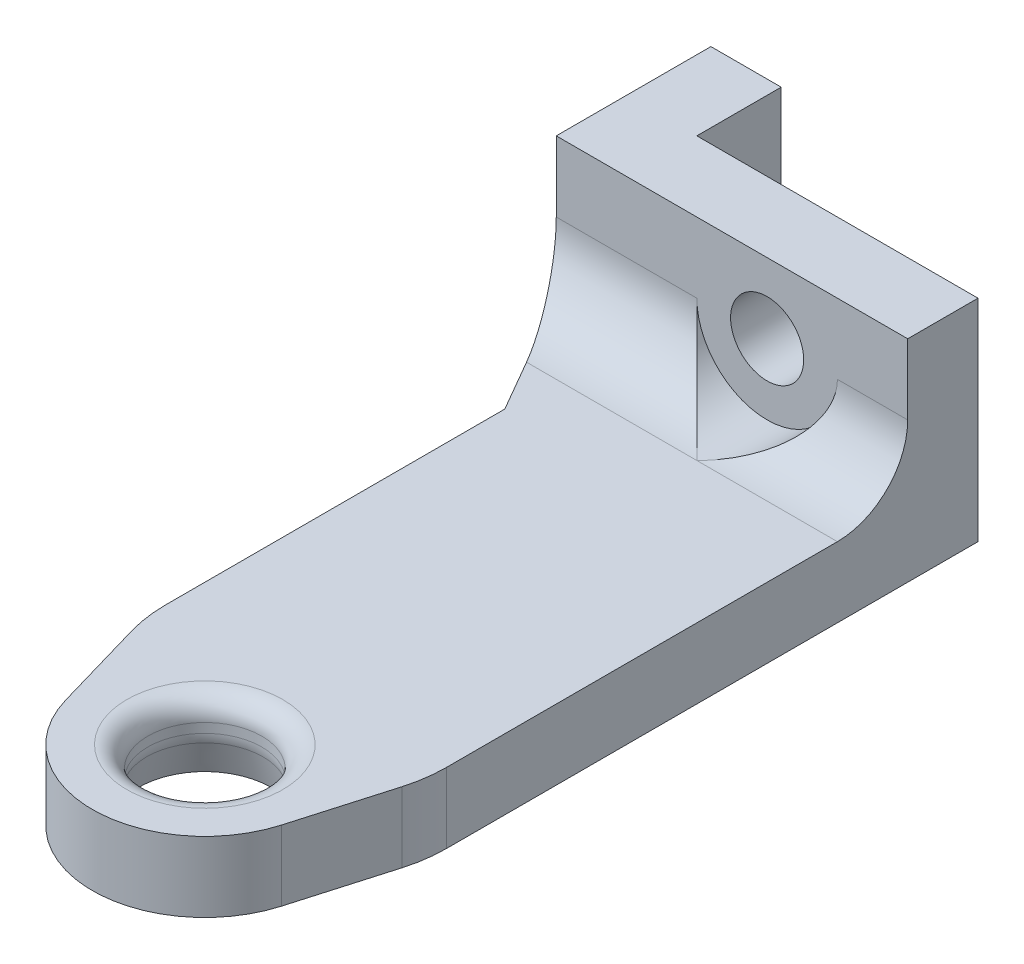
SolidWorks part; units mm, degrees
ref_plane "Front" through (0, 0, 0) normal (0, 0, 1) x (1, 0, 0)
ref_plane "Top" through (0, 0, 0) normal (0, 1, 0) x (1, 0, 0)
ref_plane "Right" through (0, 0, 0) normal (1, 0, 0) x (0, 0, -1)
sketch "Sketch1" plane through (0, 0, 0) normal (0, 1, 0) x (1, 0, 0)
  line L0 (0, 55) -> (0, 0) construction
  line L1 (-10, 45) -> (10, 45)
  line L2 (-10, 45) -> (-10, 65)
  line L3 (-10, 65) -> (10, 65)
  line L4 (10, 45) -> (10, 65)
  line L5 (-10, 45) -> (10, 65) construction
  line L6 (-10, 65) -> (10, 45) construction
  circle A0 centre (0, 0) radius 4
  point P3 (0, 55)
  dimension "D1" = 20
  dimension "D3" = 8
  dimension "D2" = 45
sketch "Sketch2" plane through (0, 0, 0) normal (0, 1, 0) x (1, 0, 0)
  line L0 (-7.6846, -2.2241) -> (-10, 5.7759)
  line L1 (-10, 5.7759) -> (-10, 45)
  line L2 (-10, 45) -> (10, 45) construction
  line L4 (0, 55) -> (0, 0) construction
  line L5 (0, 55) -> (0, 0) construction
  line L6 (10, 5.7759) -> (10, 45)
  line L7 (7.6846, -2.2241) -> (10, 5.7759)
  line L8 (-10, 45) -> (10, 45)
  circle A0 centre (0, 0) radius 8 construction
  circle A1 centre (0, 0) radius 4 construction
  arc A2 (7.6846, -2.2241) -> (-7.6846, -2.2241) centre (0, 0) cw
  circle A3 centre (0, 0) radius 4.05
  dimension "D1" = 4
  dimension "D2" = 8
  dimension "D3" = 8.1
extrude "Boss-Extrude1" add sketch "Sketch2" along normal blind 5
fillet "Fillet1" radius 10 2 edges at (10, 2.5, -5.7759) (-10, 2.5, -5.7759)
sketch "Sketch3" plane through (0, 0, -45) normal (0, 0, -1) x (-1, 0, 0)
  line L0 (10, 5) -> (10, 0) construction
  line L1 (-10, 0) -> (10, 0)
  line L2 (-10, 0) -> (-10, 15)
  line L3 (-10, 15) -> (10, 15)
  line L4 (10, 0) -> (10, 15)
  line L5 (-10, 5) -> (10, 5) construction
  dimension "D1" = 10
extrude "Boss-Extrude2" add sketch "Sketch3" against normal blind 5
sketch "Sketch6" plane through (0, 0, -40) normal (0, 0, 1) x (1, 0, 0)
  line L0 (0, 15) -> (0, 10) construction
  line L1 (-10, 15) -> (10, 15) construction
  line L2 (0, 10) -> (0, 5) construction
  line L3 (7.6846, 5) -> (-7.6846, 5) construction
  circle A0 centre (0, 10) radius 2.6
  dimension "D1" = 5.2
extrude "Cut-Extrude1" cut sketch "Sketch6" against normal through all
sketch "Sketch4" plane through (-10, 0, 0) normal (-1, 0, 0) x (0, 0, 1)
  line L0 (-40, 15) -> (-45, 15) construction
  line L1 (-40, 15) -> (-51, 15)
  line L2 (-40, 15) -> (-40, 0)
  line L3 (-40, 0) -> (-51, 0)
  line L4 (-51, 15) -> (-51, 0)
  line L5 (-40, 5) -> (-40, 15) construction
  line L6 (-45, 0) -> (-7.1939, 0) construction
  line L7 (-45, 15) -> (-45, 0) construction
  dimension "D1" = 6
extrude "Boss-Extrude3" add sketch "Sketch4" along normal blind 5
chamfer "Chamfer1" distance 5 angle 60 1 edges at (-10, 2.5, -40) first distance on face at (2.6, 10, -40)
fillet "Fillet2" radius 5 1 edges at (-2.5, 5, -40)
sketch "Sketch7" plane through (0, 0, -40) normal (0, 0, 1) x (1, 0, 0)
  circle A0 centre (0, 10) radius 5
  dimension "D1" = 10
extrude "Cut-Extrude3" cut sketch "Sketch7" along normal through all
chamfer "Chamfer2" distance 2.5 angle 15 1 edges at (0, 0, 4.05) first distance on face at (0, 5, 4.05)
fillet "Fillet3" radius 2.5 1 edges at (0, 2.5, -4.05)
fillet "Fillet4" radius 1.5 1 edges at (0, 5, 4.05)
sketch "Sketch8" plane through (0, 0, 0) normal (0, -1, 0) x (1, 0, 0)
  line L0 (3, -45) -> (3, -7) construction
  line L1 (10, -45) -> (-10, -45) construction
  line L4 (10, -7.1939) -> (10, -45) construction
  text T0 "BLR-03\r\n" font "Century Gothic" height in points 20
  dimension "D1" = 7
  dimension "D2" = 38
extrude "Cut-Extrude4" cut sketch "Sketch8" against normal blind 0.4
